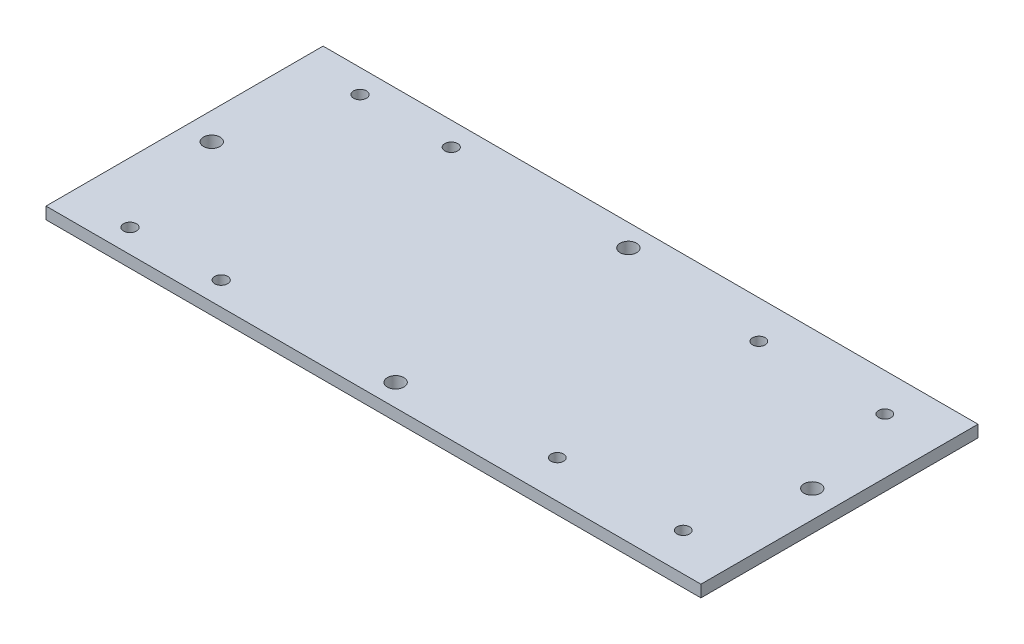
SolidWorks part; units mm, degrees
material "Thornel VCB-20 Carbon Cloth"
ref_plane "Front Plane" through (0, 0, 0) normal (0, 0, 1) x (1, 0, 0)
ref_plane "Top Plane" through (0, 0, 0) normal (0, 1, 0) x (1, 0, 0)
ref_plane "Right Plane" through (0, 0, 0) normal (1, 0, 0) x (0, 0, -1)
sketch "Sketch1" plane through (0, 0, 0) normal (0, 1, 0) x (1, 0, 0)
  line L1 (-82.55, -34.925) -> (82.55, -34.925)
  line L2 (-82.55, -34.925) -> (-82.55, 34.925)
  line L3 (-82.55, 34.925) -> (82.55, 34.925)
  line L4 (82.55, -34.925) -> (82.55, 34.925)
  dimension "D1" = 69.85
  dimension "D2" = 165.1
  dimension "D3" = 34.925
  dimension "D4" = 82.55
extrude "Boss-Extrude1" add sketch "Sketch1" along normal blind 3
sketch "Sketch2" plane through (0, 3, 0) normal (0, 1, 0) x (1, 0, 0)
  line L0 (-82.55, 34.925) -> (-82.55, -34.925) construction
  line L1 (82.55, -34.925) -> (82.55, 34.925) construction
  line L2 (82.55, 34.925) -> (-82.55, 34.925) construction
  line L3 (-82.55, -34.925) -> (82.55, -34.925) construction
  circle A0 centre (-77.47, 29.845) radius 1.5
  circle A1 centre (-77.47, -29.845) radius 1.5
  circle A2 centre (77.47, 29.845) radius 1.5
  circle A3 centre (77.47, -29.845) radius 1.5
  dimension "D1" = 3
  dimension "D2" = 3
  dimension "D3" = 3
  dimension "D4" = 3
  dimension "D5" = 5.08
  dimension "D6" = 5.08
  dimension "D7" = 5.08
  dimension "D8" = 5.08
  dimension "D9" = 5.08
  dimension "D10" = 5.08
  dimension "D11" = 5.08
  dimension "D12" = 5.08
sketch "Sketch3" plane through (0, 3, 0) normal (0, 1, 0) x (1, 0, 0)
  line L0 (-82.55, 34.925) -> (-82.55, -34.925) construction
  line L1 (82.55, -34.925) -> (82.55, 34.925) construction
  line L2 (-82.55, -34.925) -> (82.55, -34.925) construction
  line L3 (82.55, 34.925) -> (-82.55, 34.925) construction
  circle A0 centre (-75.692, 0) radius 2.0828
  circle A1 centre (75.692, 0) radius 2.0828
  circle A2 centre (0, -29.337) radius 2.0828
  circle A3 centre (0, 29.337) radius 2.0828
  point P16 (0, 0)
  point P17 (0, 0)
  point P18 (0, 0)
  dimension "D1" = 6.858
  dimension "D2" = 6.858
  dimension "D3" = 5.588
  dimension "D4" = 5.588
extrude "Cut-Extrude2" cut sketch "Sketch3" against normal blind 5.08
sketch "Sketch4" plane through (0, 3, 0) normal (0, 1, 0) x (1, 0, 0)
  line L0 (-82.55, 34.925) -> (-82.55, -34.925) construction
  line L1 (-44.31, -29) -> (-67.31, -29) construction
  line L2 (-44.31, -29) -> (-44.31, 29) construction
  line L3 (-44.31, 29) -> (-67.31, 29) construction
  line L4 (-67.31, -29) -> (-67.31, 29) construction
  line L5 (-44.31, -29) -> (-67.31, 29) construction
  line L6 (-44.31, 29) -> (-67.31, -29) construction
  circle A0 centre (-67.31, 29) radius 1.625
  circle A1 centre (-44.31, 29) radius 1.625
  circle A2 centre (-44.31, -29) radius 1.625
  circle A3 centre (-67.31, -29) radius 1.625
  point P0 (-55.81, 0)
  point P8 (-35.4796, 29)
  point P10 (0, 0)
  point P11 (-37.5555, -30.15)
  point P13 (-58.4114, -29)
  dimension "D3" = 3.25
  dimension "D1" = 58
  dimension "D2" = 23
  dimension "D4" = 15.24
extrude "Cut-Extrude3" cut sketch "Sketch4" against normal blind 17.78
sketch "Sketch5" plane through (0, 3, 0) normal (0, 1, 0) x (1, 0, 0)
  line L0 (82.55, 34.925) -> (-82.55, 34.925) construction
  line L1 (68.58, -25.4) -> (36.83, -25.4) construction
  line L2 (68.58, -25.4) -> (68.58, 25.4) construction
  line L3 (68.58, 25.4) -> (36.83, 25.4) construction
  line L4 (36.83, -25.4) -> (36.83, 25.4) construction
  line L5 (68.58, -25.4) -> (36.83, 25.4) construction
  line L6 (68.58, 25.4) -> (36.83, -25.4) construction
  line L7 (-82.55, -34.925) -> (82.55, -34.925) construction
  line L8 (82.55, -34.925) -> (82.55, 34.925) construction
  circle A0 centre (68.58, -25.4) radius 1.5875
  circle A2 centre (68.58, 25.4) radius 1.5875
  circle A3 centre (36.83, 25.4) radius 1.5875
  circle A4 centre (36.83, -25.4) radius 1.5875
  point P0 (52.705, 0)
  point P12 (36.9889, 24.6043)
  point P14 (0, 0)
  point P17 (43.6961, 24.6813)
  point P18 (37.4037, -25.4)
  point P20 (68.58, -26.0404)
  dimension "D1" = 9.525
  dimension "D3" = 3.175
  dimension "D2" = 9.525
  dimension "D4" = 31.75
  dimension "D5" = 13.97
extrude "Cut-Extrude4" cut sketch "Sketch5" against normal blind 7.874
